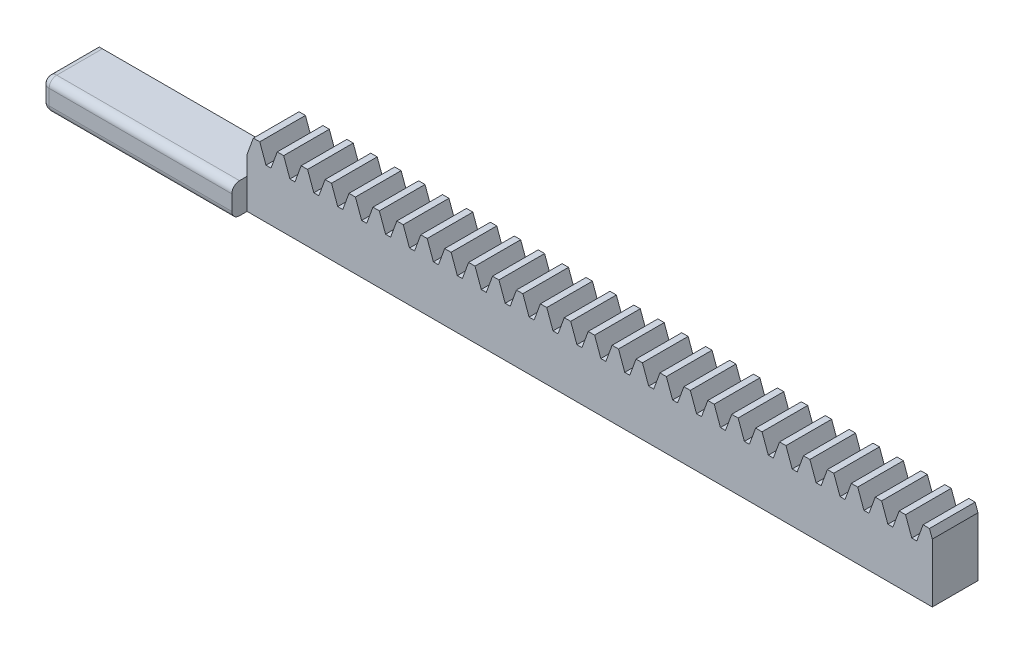
SolidWorks part; units mm, degrees
ref_plane "前视基准面" through (0, 0, 0) normal (0, 0, 1) x (1, 0, 0)
ref_plane "上视基准面" through (0, 0, 0) normal (0, 1, 0) x (1, 0, 0)
ref_plane "右视基准面" through (0, 0, 0) normal (1, 0, 0) x (0, 0, -1)
sketch "草图1" plane through (0, 0, 0) normal (0, 0, 1) x (1, 0, 0)
  line L1 (0, 0) -> (135.0885, 0)
  line L2 (0, 0) -> (0, -6.5)
  line L3 (0, -6.5) -> (135.0885, -6.5)
  line L4 (135.0885, 0) -> (135.0885, -6.5)
  dimension "D1" = 6.5
  dimension "L" = 135.0885
extrude "拉伸1" add sketch "草图1" along normal blind 8
sketch "草图2" plane through (0, 0, 8) normal (0, 0, 1) x (1, 0, 0)
  line L0 (0, 0) -> (0.8189, 2.25)
  line L1 (0.8189, 2.25) -> (1.6618, 2.25)
  line L2 (1.6618, 2.25) -> (2.4807, 0)
  line L3 (135.0885, 0) -> (0, 0) construction
  line L4 (0, 0) -> (2.4807, 0)
  line L5 (0.455, 1.25) -> (2.0258, 1.25) construction
  dimension "D2" = 70
  dimension "alpha" = 110
  dimension "ha" = 1
  dimension "hf" = 1.25
  dimension "S" = 1.5708
extrude "拉伸2" add sketch "草图2" against normal up to surface (8 mm away) up to face at (67.5442, -3.25, 0)
pattern_linear "阵列(线性)1" count 43 spacing 3.1416 along (1, 0, 0) of "拉伸2"
sketch "草图3" plane through (0, 0, 8) normal (0, 0, 1) x (1, 0, 0)
  line L1 (0, -6.5) -> (90, -6.5)
  line L2 (0, -6.5) -> (0, 22.1264)
  line L3 (0, 22.1264) -> (90, 22.1264)
  line L4 (90, -6.5) -> (90, 22.1264)
  dimension "D1" = 90
extrude "切除-拉伸1" cut sketch "草图3" against normal blind 26 flip side to cut
sketch "草图4" plane through (90, 0, 0) normal (1, 0, 0) x (0, 0, -1)
  line L0 (0, -6.5) -> (0, 1.2235) construction
  line L1 (-8, -6.5) -> (0, -6.5)
  line L2 (-8, -6.5) -> (-8, -2.5)
  line L3 (-8, -2.5) -> (0, -2.5)
  line L4 (0, -6.5) -> (0, -2.5)
  dimension "D1" = 4
extrude "凸台-拉伸1" add sketch "草图4" against normal offset from surface (115 mm away) 25 up to face at (0, -3.25, 4) offset beyond the face yes
sketch "草图5" plane through (0, 0, 8) normal (0, 0, 1) x (1, 0, 0)
  line L120 (0, 0) -> (0, -2.5)
  line L121 (0, -2.5) -> (-25, -2.5)
  line L122 (-25, -2.5) -> (-25, -6.5)
  line L123 (-25, -6.5) -> (90, -6.5)
  line L124 (90, -6.5) -> (90, 1.2235)
  line L125 (90, 1.2235) -> (89.6264, 2.25)
  line L126 (89.6264, 2.25) -> (88.7835, 2.25)
  line L127 (88.7835, 2.25) -> (87.9646, 0)
  line L128 (87.9646, 0) -> (87.3037, 0)
  line L129 (87.3037, 0) -> (86.4848, 2.25)
  line L130 (86.4848, 2.25) -> (85.6419, 2.25)
  line L131 (85.6419, 2.25) -> (84.823, 0)
  line L132 (84.823, 0) -> (84.1621, 0)
  line L133 (84.1621, 0) -> (83.3432, 2.25)
  line L134 (83.3432, 2.25) -> (82.5003, 2.25)
  line L135 (82.5003, 2.25) -> (81.6814, 0)
  line L136 (81.6814, 0) -> (81.0205, 0)
  line L137 (81.0205, 0) -> (80.2016, 2.25)
  line L138 (80.2016, 2.25) -> (79.3587, 2.25)
  line L139 (79.3587, 2.25) -> (78.5398, 0)
  line L140 (78.5398, 0) -> (77.8789, 0)
  line L141 (77.8789, 0) -> (77.06, 2.25)
  line L142 (77.06, 2.25) -> (76.2172, 2.25)
  line L143 (76.2172, 2.25) -> (75.3982, 0)
  line L144 (75.3982, 0) -> (74.7374, 0)
  line L145 (74.7374, 0) -> (73.9184, 2.25)
  line L146 (73.9184, 2.25) -> (73.0756, 2.25)
  line L147 (73.0756, 2.25) -> (72.2566, 0)
  line L148 (72.2566, 0) -> (71.5958, 0)
  line L149 (71.5958, 0) -> (70.7768, 2.25)
  line L150 (70.7768, 2.25) -> (69.934, 2.25)
  line L151 (69.934, 2.25) -> (69.115, 0)
  line L152 (69.115, 0) -> (68.4542, 0)
  line L153 (68.4542, 0) -> (67.6352, 2.25)
  line L154 (67.6352, 2.25) -> (66.7924, 2.25)
  line L155 (66.7924, 2.25) -> (65.9734, 0)
  line L156 (65.9734, 0) -> (65.3126, 0)
  line L157 (65.3126, 0) -> (64.4936, 2.25)
  line L158 (64.4936, 2.25) -> (63.6508, 2.25)
  line L159 (63.6508, 2.25) -> (62.8319, 0)
  line L160 (62.8319, 0) -> (62.171, 0)
  line L161 (62.171, 0) -> (61.352, 2.25)
  line L162 (61.352, 2.25) -> (60.5092, 2.25)
  line L163 (60.5092, 2.25) -> (59.6903, 0)
  line L164 (59.6903, 0) -> (59.0294, 0)
  line L165 (59.0294, 0) -> (58.2105, 2.25)
  line L166 (58.2105, 2.25) -> (57.3676, 2.25)
  line L167 (57.3676, 2.25) -> (56.5487, 0)
  line L168 (56.5487, 0) -> (55.8878, 0)
  line L169 (55.8878, 0) -> (55.0689, 2.25)
  line L170 (55.0689, 2.25) -> (54.226, 2.25)
  line L171 (54.226, 2.25) -> (53.4071, 0)
  line L172 (53.4071, 0) -> (52.7462, 0)
  line L173 (52.7462, 0) -> (51.9273, 2.25)
  line L174 (51.9273, 2.25) -> (51.0844, 2.25)
  line L175 (51.0844, 2.25) -> (50.2655, 0)
  line L176 (50.2655, 0) -> (49.6046, 0)
  line L177 (49.6046, 0) -> (48.7857, 2.25)
  line L178 (48.7857, 2.25) -> (47.9428, 2.25)
  line L179 (47.9428, 2.25) -> (47.1239, 0)
  line L180 (47.1239, 0) -> (46.463, 0)
  line L181 (46.463, 0) -> (45.6441, 2.25)
  line L182 (45.6441, 2.25) -> (44.8012, 2.25)
  line L183 (44.8012, 2.25) -> (43.9823, 0)
  line L184 (43.9823, 0) -> (43.3214, 0)
  line L185 (43.3214, 0) -> (42.5025, 2.25)
  line L186 (42.5025, 2.25) -> (41.6596, 2.25)
  line L187 (41.6596, 2.25) -> (40.8407, 0)
  line L188 (40.8407, 0) -> (40.1798, 0)
  line L189 (40.1798, 0) -> (39.3609, 2.25)
  line L190 (39.3609, 2.25) -> (38.518, 2.25)
  line L191 (38.518, 2.25) -> (37.6991, 0)
  line L192 (37.6991, 0) -> (37.0382, 0)
  line L193 (37.0382, 0) -> (36.2193, 2.25)
  line L194 (36.2193, 2.25) -> (35.3765, 2.25)
  line L195 (35.3765, 2.25) -> (34.5575, 0)
  line L196 (34.5575, 0) -> (33.8966, 0)
  line L197 (33.8966, 0) -> (33.0777, 2.25)
  line L198 (33.0777, 2.25) -> (32.2349, 2.25)
  line L199 (32.2349, 2.25) -> (31.4159, 0)
  line L200 (31.4159, 0) -> (30.7551, 0)
  line L201 (30.7551, 0) -> (29.9361, 2.25)
  line L202 (29.9361, 2.25) -> (29.0933, 2.25)
  line L203 (29.0933, 2.25) -> (28.2743, 0)
  line L204 (28.2743, 0) -> (27.6135, 0)
  line L205 (27.6135, 0) -> (26.7945, 2.25)
  line L206 (26.7945, 2.25) -> (25.9517, 2.25)
  line L207 (25.9517, 2.25) -> (25.1327, 0)
  line L208 (25.1327, 0) -> (24.4719, 0)
  line L209 (24.4719, 0) -> (23.6529, 2.25)
  line L210 (23.6529, 2.25) -> (22.8101, 2.25)
  line L211 (22.8101, 2.25) -> (21.9911, 0)
  line L212 (21.9911, 0) -> (21.3303, 0)
  line L213 (21.3303, 0) -> (20.5113, 2.25)
  line L214 (20.5113, 2.25) -> (19.6685, 2.25)
  line L215 (19.6685, 2.25) -> (18.8496, 0)
  line L216 (18.8496, 0) -> (18.1887, 0)
  line L217 (18.1887, 0) -> (17.3698, 2.25)
  line L218 (17.3698, 2.25) -> (16.5269, 2.25)
  line L219 (16.5269, 2.25) -> (15.708, 0)
  line L220 (15.708, 0) -> (15.0471, 0)
  line L221 (15.0471, 0) -> (14.2282, 2.25)
  line L222 (14.2282, 2.25) -> (13.3853, 2.25)
  line L223 (13.3853, 2.25) -> (12.5664, 0)
  line L224 (12.5664, 0) -> (11.9055, 0)
  line L225 (11.9055, 0) -> (11.0866, 2.25)
  line L226 (11.0866, 2.25) -> (10.2437, 2.25)
  line L227 (10.2437, 2.25) -> (9.4248, 0)
  line L228 (9.4248, 0) -> (8.7639, 0)
  line L229 (8.7639, 0) -> (7.945, 2.25)
  line L230 (7.945, 2.25) -> (7.1021, 2.25)
  line L231 (7.1021, 2.25) -> (6.2832, 0)
  line L232 (6.2832, 0) -> (5.6223, 0)
  line L233 (5.6223, 0) -> (4.8034, 2.25)
  line L234 (4.8034, 2.25) -> (3.9605, 2.25)
  line L235 (3.9605, 2.25) -> (3.1416, 0)
  line L236 (3.1416, 0) -> (2.4807, 0)
  line L237 (2.4807, 0) -> (1.6618, 2.25)
  line L238 (1.6618, 2.25) -> (0.8189, 2.25)
  line L239 (0.8189, 2.25) -> (0, 0)
  line L240 (0, 0) -> (0, -2.5)
  line L241 (0, -2.5) -> (-25, -2.5)
  line L242 (-25, -2.5) -> (-25, -6.5)
  line L243 (-25, -6.5) -> (90, -6.5)
  line L244 (90, -6.5) -> (90, 1.2235)
  line L245 (90, 1.2235) -> (89.6264, 2.25)
  line L246 (89.6264, 2.25) -> (88.7835, 2.25)
  line L247 (88.7835, 2.25) -> (87.9646, 0)
  line L248 (87.9646, 0) -> (87.3037, 0)
  line L249 (87.3037, 0) -> (86.4848, 2.25)
  line L250 (86.4848, 2.25) -> (85.6419, 2.25)
  line L251 (85.6419, 2.25) -> (84.823, 0)
  line L252 (84.823, 0) -> (84.1621, 0)
  line L253 (84.1621, 0) -> (83.3432, 2.25)
  line L254 (83.3432, 2.25) -> (82.5003, 2.25)
  line L255 (82.5003, 2.25) -> (81.6814, 0)
  line L256 (81.6814, 0) -> (81.0205, 0)
  line L257 (81.0205, 0) -> (80.2016, 2.25)
  line L258 (80.2016, 2.25) -> (79.3587, 2.25)
  line L259 (79.3587, 2.25) -> (78.5398, 0)
  line L260 (78.5398, 0) -> (77.8789, 0)
  line L261 (77.8789, 0) -> (77.06, 2.25)
  line L262 (77.06, 2.25) -> (76.2172, 2.25)
  line L263 (76.2172, 2.25) -> (75.3982, 0)
  line L264 (75.3982, 0) -> (74.7374, 0)
  line L265 (74.7374, 0) -> (73.9184, 2.25)
  line L266 (73.9184, 2.25) -> (73.0756, 2.25)
  line L267 (73.0756, 2.25) -> (72.2566, 0)
  line L268 (72.2566, 0) -> (71.5958, 0)
  line L269 (71.5958, 0) -> (70.7768, 2.25)
  line L270 (70.7768, 2.25) -> (69.934, 2.25)
  line L271 (69.934, 2.25) -> (69.115, 0)
  line L272 (69.115, 0) -> (68.4542, 0)
  line L273 (68.4542, 0) -> (67.6352, 2.25)
  line L274 (67.6352, 2.25) -> (66.7924, 2.25)
  line L275 (66.7924, 2.25) -> (65.9734, 0)
  line L276 (65.9734, 0) -> (65.3126, 0)
  line L277 (65.3126, 0) -> (64.4936, 2.25)
  line L278 (64.4936, 2.25) -> (63.6508, 2.25)
  line L279 (63.6508, 2.25) -> (62.8319, 0)
  line L280 (62.8319, 0) -> (62.171, 0)
  line L281 (62.171, 0) -> (61.352, 2.25)
  line L282 (61.352, 2.25) -> (60.5092, 2.25)
  line L283 (60.5092, 2.25) -> (59.6903, 0)
  line L284 (59.6903, 0) -> (59.0294, 0)
  line L285 (59.0294, 0) -> (58.2105, 2.25)
  line L286 (58.2105, 2.25) -> (57.3676, 2.25)
  line L287 (57.3676, 2.25) -> (56.5487, 0)
  line L288 (56.5487, 0) -> (55.8878, 0)
  line L289 (55.8878, 0) -> (55.0689, 2.25)
  line L290 (55.0689, 2.25) -> (54.226, 2.25)
  line L291 (54.226, 2.25) -> (53.4071, 0)
  line L292 (53.4071, 0) -> (52.7462, 0)
  line L293 (52.7462, 0) -> (51.9273, 2.25)
  line L294 (51.9273, 2.25) -> (51.0844, 2.25)
  line L295 (51.0844, 2.25) -> (50.2655, 0)
  line L296 (50.2655, 0) -> (49.6046, 0)
  line L297 (49.6046, 0) -> (48.7857, 2.25)
  line L298 (48.7857, 2.25) -> (47.9428, 2.25)
  line L299 (47.9428, 2.25) -> (47.1239, 0)
  line L300 (47.1239, 0) -> (46.463, 0)
  line L301 (46.463, 0) -> (45.6441, 2.25)
  line L302 (45.6441, 2.25) -> (44.8012, 2.25)
  line L303 (44.8012, 2.25) -> (43.9823, 0)
  line L304 (43.9823, 0) -> (43.3214, 0)
  line L305 (43.3214, 0) -> (42.5025, 2.25)
  line L306 (42.5025, 2.25) -> (41.6596, 2.25)
  line L307 (41.6596, 2.25) -> (40.8407, 0)
  line L308 (40.8407, 0) -> (40.1798, 0)
  line L309 (40.1798, 0) -> (39.3609, 2.25)
  line L310 (39.3609, 2.25) -> (38.518, 2.25)
  line L311 (38.518, 2.25) -> (37.6991, 0)
  line L312 (37.6991, 0) -> (37.0382, 0)
  line L313 (37.0382, 0) -> (36.2193, 2.25)
  line L314 (36.2193, 2.25) -> (35.3765, 2.25)
  line L315 (35.3765, 2.25) -> (34.5575, 0)
  line L316 (34.5575, 0) -> (33.8966, 0)
  line L317 (33.8966, 0) -> (33.0777, 2.25)
  line L318 (33.0777, 2.25) -> (32.2349, 2.25)
  line L319 (32.2349, 2.25) -> (31.4159, 0)
  line L320 (31.4159, 0) -> (30.7551, 0)
  line L321 (30.7551, 0) -> (29.9361, 2.25)
  line L322 (29.9361, 2.25) -> (29.0933, 2.25)
  line L323 (29.0933, 2.25) -> (28.2743, 0)
  line L324 (28.2743, 0) -> (27.6135, 0)
  line L325 (27.6135, 0) -> (26.7945, 2.25)
  line L326 (26.7945, 2.25) -> (25.9517, 2.25)
  line L327 (25.9517, 2.25) -> (25.1327, 0)
  line L328 (25.1327, 0) -> (24.4719, 0)
  line L329 (24.4719, 0) -> (23.6529, 2.25)
  line L330 (23.6529, 2.25) -> (22.8101, 2.25)
  line L331 (22.8101, 2.25) -> (21.9911, 0)
  line L332 (21.9911, 0) -> (21.3303, 0)
  line L333 (21.3303, 0) -> (20.5113, 2.25)
  line L334 (20.5113, 2.25) -> (19.6685, 2.25)
  line L335 (19.6685, 2.25) -> (18.8496, 0)
  line L336 (18.8496, 0) -> (18.1887, 0)
  line L337 (18.1887, 0) -> (17.3698, 2.25)
  line L338 (17.3698, 2.25) -> (16.5269, 2.25)
  line L339 (16.5269, 2.25) -> (15.708, 0)
  line L340 (15.708, 0) -> (15.0471, 0)
  line L341 (15.0471, 0) -> (14.2282, 2.25)
  line L342 (14.2282, 2.25) -> (13.3853, 2.25)
  line L343 (13.3853, 2.25) -> (12.5664, 0)
  line L344 (12.5664, 0) -> (11.9055, 0)
  line L345 (11.9055, 0) -> (11.0866, 2.25)
  line L346 (11.0866, 2.25) -> (10.2437, 2.25)
  line L347 (10.2437, 2.25) -> (9.4248, 0)
  line L348 (9.4248, 0) -> (8.7639, 0)
  line L349 (8.7639, 0) -> (7.945, 2.25)
  line L350 (7.945, 2.25) -> (7.1021, 2.25)
  line L351 (7.1021, 2.25) -> (6.2832, 0)
  line L352 (6.2832, 0) -> (5.6223, 0)
  line L353 (5.6223, 0) -> (4.8034, 2.25)
  line L354 (4.8034, 2.25) -> (3.9605, 2.25)
  line L355 (3.9605, 2.25) -> (3.1416, 0)
  line L356 (3.1416, 0) -> (2.4807, 0)
  line L357 (2.4807, 0) -> (1.6618, 2.25)
  line L358 (1.6618, 2.25) -> (0.8189, 2.25)
  line L359 (0.8189, 2.25) -> (0, 0)
  dimension "D1" = 0
extrude "切除-拉伸2" cut sketch "草图5" against normal blind 2
sketch "草图6" plane through (0, 0, 0) normal (0, 0, -1) x (-1, 0, 0)
  line L1 (0, -2.5) -> (25, -2.5)
  line L2 (0, -2.5) -> (0, -6.5)
  line L3 (0, -6.5) -> (25, -6.5)
  line L4 (25, -2.5) -> (25, -6.5)
extrude "凸台-拉伸2" [suppressed] add sketch "草图6" along normal blind 2
sketch "草图7" plane through (0, 0, 6) normal (0, 0, 1) x (1, 0, 0)
  line L1 (0, -2.5) -> (-25, -2.5)
  line L2 (0, -2.5) -> (0, -6.5)
  line L3 (0, -6.5) -> (-25, -6.5)
  line L4 (-25, -2.5) -> (-25, -6.5)
extrude "凸台-拉伸3" add sketch "草图7" along normal blind 2
fillet "圆角1" radius 1 2 edges at (-12.5, -6.5, 8) (-12.5, -2.5, 8)
fillet "圆角2" radius 1 5 edges at (-25, -2.5, 3.5) (-25, -2.7929, 7.7071) (-25, -6.5, 3.5) (-25, -6.2071, 7.7071) (-25, -4.5, 8)
chamfer "倒角1" distance 1 angle 45 1 edges at (-12, -2.5, 0) tangent propagation no
equation "\"d\"=\"S@草图2\" * 2"
equation "\"z\"= int(  \"L@草图1\" / (  \"S@草图2\" * 2 ) + 0.5 )"
